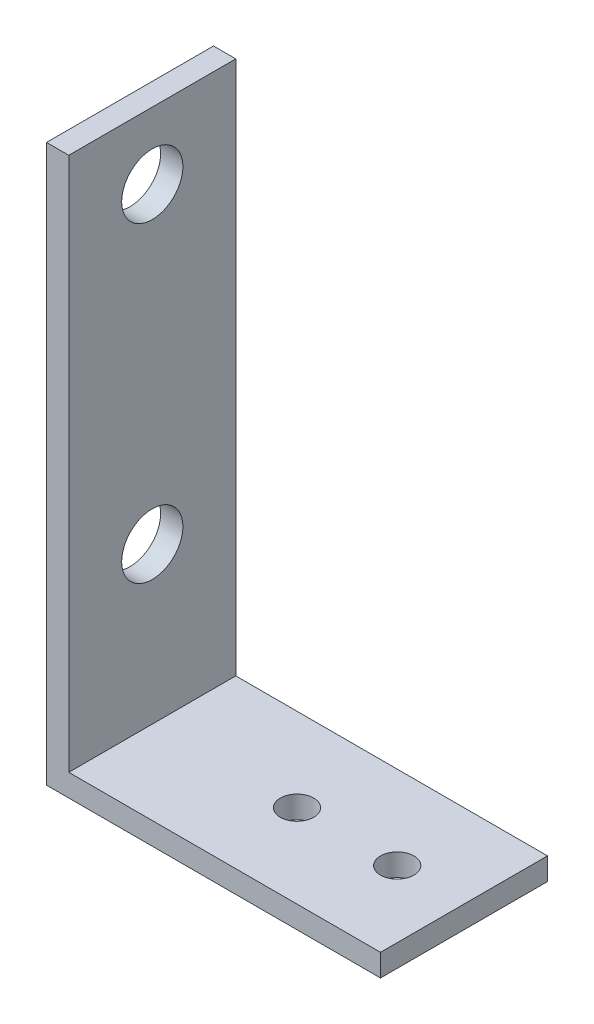
SolidWorks part; units mm, degrees
ref_plane "Piano frontale" through (0, 0, 0) normal (0, 0, 1) x (1, 0, 0)
ref_plane "Piano superiore" through (0, 0, 0) normal (0, 1, 0) x (1, 0, 0)
ref_plane "Piano destro" through (0, 0, 0) normal (1, 0, 0) x (0, 0, -1)
sketch "Schizzo1" plane through (0, 0, 0) normal (0, 0, 1) x (1, 0, 0)
  line L0 (0, 0) -> (-30, 0)
  line L1 (-30, 0) -> (-30, 50)
  line L2 (-30, 50) -> (-28, 50)
  line L3 (-28, 50) -> (-28, 2)
  line L4 (-28, 2) -> (0, 2)
  line L5 (0, 2) -> (0, 0)
  dimension "D1" = 50
  dimension "D2" = 2
  dimension "D3" = 30
  dimension "D4" = 2
extrude "Estrusione-Estrusione1" add sketch "Schizzo1" along normal blind 15
sketch "Schizzo2" plane through (-30, 0, 0) normal (-1, 0, 0) x (0, 0, 1)
  line L0 (7.5, 50) -> (7.5, 0) construction
  line L1 (15, 50) -> (0, 50) construction
  line L2 (15, 0) -> (0, 0) construction
  circle A0 centre (7.5, 44) radius 2.75
  circle A1 centre (7.5, 16) radius 2.75
  dimension "D2" = 5.5
  dimension "D3" = 5.5
  dimension "D1" = 28
  dimension "D4" = 6
extrude "Taglio-Estrusione1" cut sketch "Schizzo2" against normal blind 15
sketch "Schizzo3" plane through (0, 0, 0) normal (0, -1, 0) x (1, 0, 0)
  line L0 (0, 7.5) -> (-30, 7.5) construction
  line L1 (0, 15) -> (0, 0) construction
  line L2 (-30, 15) -> (-30, 0) construction
  circle A0 centre (-6, 7.5) radius 1.5
  circle A1 centre (-15, 7.5) radius 1.5
  dimension "D1" = 3
  dimension "D2" = 3
  dimension "D3" = 9
  dimension "D4" = 6
extrude "Taglio-Estrusione2" cut sketch "Schizzo3" against normal blind 15
